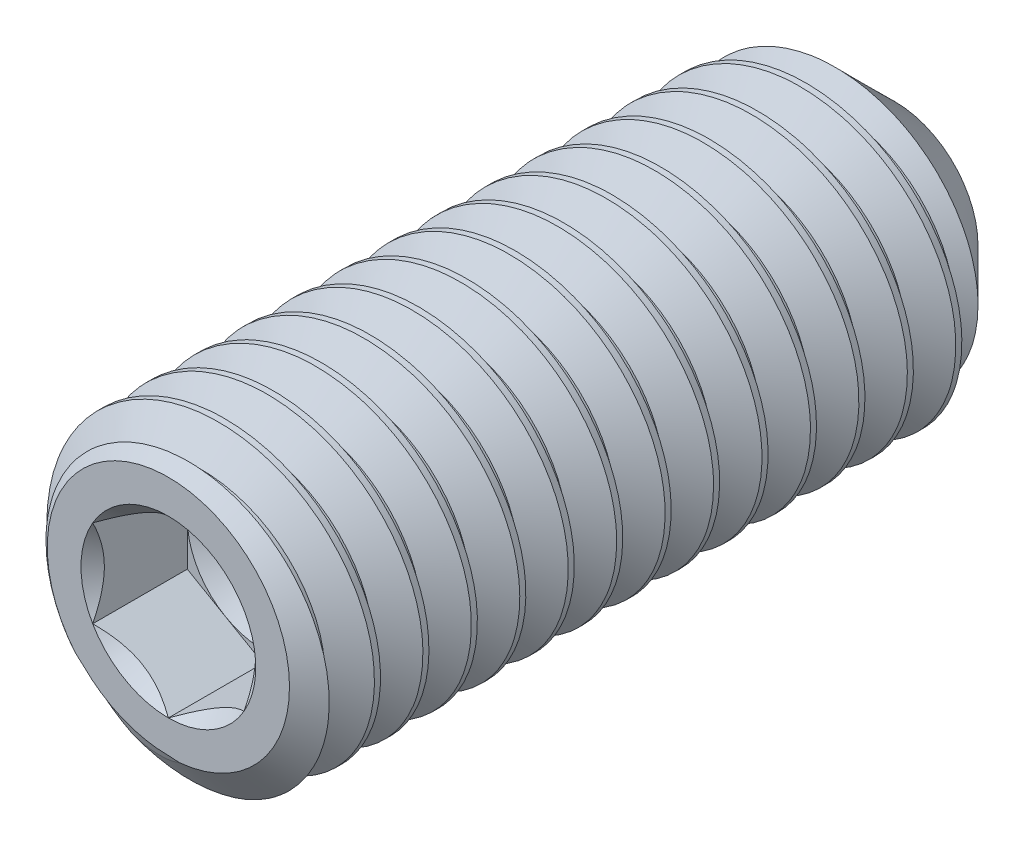
SolidWorks part; units mm, degrees
ref_plane "Front" through (0, 0, 0) normal (0, 0, 1) x (1, 0, 0)
ref_plane "Top" through (0, 0, 0) normal (0, 1, 0) x (1, 0, 0)
ref_plane "Right" through (0, 0, 0) normal (1, 0, 0) x (0, 0, -1)
sketch "Sketch22" plane through (0, 0, 0) normal (1, 0, 0) x (0, 0, -1)
  line L0 (-5.5884, 0) -> (-5.5884, 2)
  line L1 (-5.5884, 2) -> (-5.2383, 2.5)
  line L2 (-5.2383, 2.5) -> (5.2815, 2.5)
  line L3 (5.2815, 2.5) -> (6.4116, 1.3699)
  line L4 (6.4116, 1.3699) -> (5.5884, 0)
  line L5 (5.5884, 0) -> (-5.5884, 0)
  line L6 (5.5884, 0) -> (6.4116, 0) construction
  line L7 (6.4116, 0) -> (6.4116, 1.3699) construction
  line L8 (6.4116, -1.3699) -> (5.5884, 0) construction
  line L9 (-5.2383, -2.5) -> (5.2815, -2.5) construction
  dimension "Dia" = 5
  dimension "Length" = 12
  dimension "D3" = 35
  dimension "D5" = 118
  dimension "D6" = 45
  dimension "D7" = 4
revolve "Revolve1" add sketch "Sketch22" angle 360 about L6
ref_plane "Plane1" through (0, 0, -6.4116) normal (0, 0, 1) x (1, 0, 0)
sketch "Sketch27" plane through (0, 0, -6.4116) normal (0, 0, 1) x (1, 0, 0)
  circle A0 centre (0, 0) radius 2.5 construction
  circle A1 centre (0, 0) radius 2.5
curve "Helix/Spiral1" pitch 0.8 height 12.8 radius 2.5 centre (0, 0, -6.4116) axis (0, 0, 1) start towards (0, 1, 0)
sketch "Sketch28" plane through (0, 0, 0) normal (1, 0, 0) x (0, 0, -1)
  line L0 (6.4116, 2.5) -> (7.1116, 2.5)
  line L1 (7.1116, 2.5) -> (6.8116, 1.9804)
  line L2 (6.8116, 1.9804) -> (6.7116, 1.9804)
  line L3 (6.7116, 1.9804) -> (6.4116, 2.5)
  line L4 (6.5616, 2.2402) -> (6.9616, 2.2402) construction
  line L6 (-5.2383, 2.5) -> (5.2815, 2.5) construction
  dimension "D1" = 0.1
  dimension "D3" = 60
  dimension "D2" = 0.4
sweep "Cut-Sweep2" cut profiles "Sketch28" path "Helix/Spiral1" align with end faces yes
sketch "Sketch23" plane through (0, 0, 5.5884) normal (0, 0, 1) x (1, 0, 0)
  line L1 (0, 1.4434) -> (-1.25, 0.7217)
  line L2 (-1.25, 0.7217) -> (-1.25, -0.7217)
  line L3 (-1.25, -0.7217) -> (0, -1.4434)
  line L4 (0, -1.4434) -> (1.25, -0.7217)
  line L5 (1.25, -0.7217) -> (1.25, 0.7217)
  line L6 (1.25, 0.7217) -> (0, 1.4434)
  circle A0 centre (0, 0) radius 1.25 construction
  dimension "Hex" = 2.5
extrude "Cut-Extrude10" cut sketch "Sketch23" against normal blind 1.5625
sketch "Sketch24" plane through (0, 0, 5.5884) normal (0, 0, 1) x (1, 0, 0)
  circle A0 centre (0, 0) radius 1.4434
extrude "Cut-Extrude11" cut sketch "Sketch24" against normal through all draft 45
sketch "Sketch26" plane through (0, 0, 4.0259) normal (0, 0, 1) x (1, 0, 0)
  circle A0 centre (0, 0) radius 1.25 construction
  circle A1 centre (0, 0) radius 1.25
extrude "Cut-Extrude12" cut sketch "Sketch26" against normal through all draft 60
sketch "Sketch30" plane through (0, 0, 0) normal (1, 0, 0) x (0, 0, -1)
  line L0 (-5.2383, 2.5) -> (5.2815, 2.5) construction
  line L1 (-5.5884, 0) -> (-5.5884, 2) construction
  line L2 (6.4116, 0) -> (6.4116, 1.3699) construction
  line L3 (-5.2383, -2.5) -> (5.2815, -2.5) construction
  point P0 (-5.5884, 2.5)
  point P1 (6.4116, 2.5)
  point P2 (6.4116, -2.5)
  point P11 (5.2116, -2.5)
  dimension "D1" = 1.2
sketch "Sketch31" plane through (0, 0, 0) normal (1, 0, 0) x (0, 0, -1)
  line L2 (5.5884, 0) -> (6.4116, -1.3699)
  line L3 (6.4116, 1.3699) -> (5.5884, 0)
equation "\"D7@Sketch22\"=\"Dia@Sketch22\"*.8"
equation "\"D1@Sketch28\" = \"D4@Helix/Spiral1\" * .125"
equation "\"D2@Sketch28\" = \"D4@Helix/Spiral1\" * .5"
equation "\"D3@Helix/Spiral1\" = \"Length@Sketch22\" + \"D4@Helix/Spiral1\""
equation "\"D1@Sketch30\" = \"D4@Helix/Spiral1\" * 1.5"
equation "\"hex Depth@Cut-Extrude10\" = \"Hex@Sketch23\" * .625"
